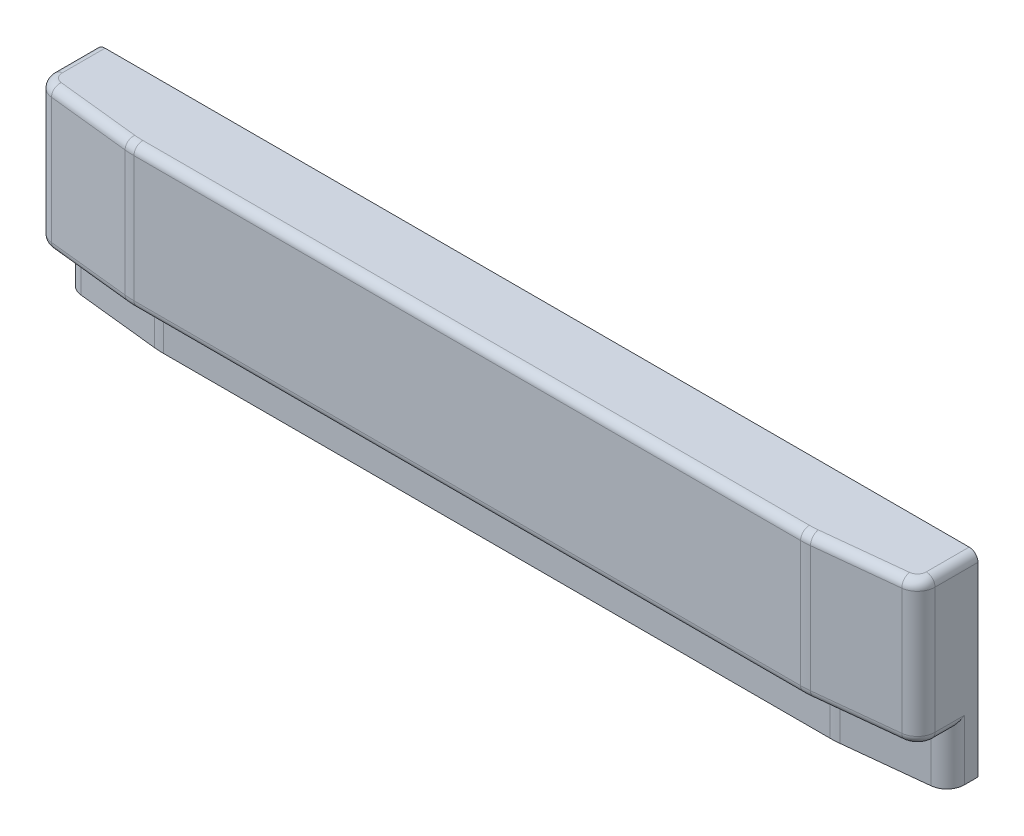
SolidWorks part; units mm, degrees
ref_plane "Front Plane" through (0, 0, 0) normal (0, 0, 1) x (1, 0, 0)
ref_plane "Top Plane" through (0, 0, 0) normal (0, 1, 0) x (1, 0, 0)
ref_plane "Right Plane" through (0, 0, 0) normal (1, 0, 0) x (0, 0, -1)
sketch "Sketch7" plane through (0, 0, 0) normal (0, 1, 0) x (1, 0, 0)
  line L0 (0, 0) -> (762, 0)
  line L1 (762, 0) -> (762, -50.8)
  line L2 (762, -50.8) -> (673.1, -60.325)
  line L3 (673.1, -60.325) -> (88.9, -60.325)
  line L4 (88.9, -60.325) -> (0, -50.8)
  line L5 (0, -50.8) -> (0, 0)
  dimension "D1" = 762
  dimension "D2" = 50.8
  dimension "D3" = 88.9
  dimension "D4" = 88.9
  dimension "D5" = 60.325
extrude "Boss-Extrude1" add sketch "Sketch7" along normal blind 168.275
ref_plane "Wall Plane" through (0, 0, 0) normal (0, 0, 1) x (1, 0, 0)
ref_plane "Floor Plane" through (0, 0, 0) normal (0, 1, 0) x (1, 0, 0)
sketch "Sketch10" plane through (0, 0, 0) normal (0, -1, 0) x (1, 0, 0)
  line L0 (0, 50.8) -> (0, 25.4)
  line L1 (0, 0) -> (0, 50.8) construction
  line L2 (0, 25.4) -> (88.9, 34.925)
  line L3 (88.9, 34.925) -> (673.1, 34.925)
  line L4 (673.1, 34.925) -> (762, 25.4)
  line L5 (762, 50.8) -> (762, 0) construction
  line L6 (762, 25.4) -> (762, 50.8)
  line L7 (762, 50.8) -> (673.1, 60.325)
  line L8 (673.1, 60.325) -> (88.9, 60.325)
  line L9 (88.9, 60.325) -> (0, 50.8)
  dimension "D1" = 25.4
extrude "Cut-Extrude1" cut sketch "Sketch10" against normal blind 44.45
fillet "Fillet1" radius 15.24 4 edges at (762, 22.225, 25.4) (762, 106.3625, 50.8) (0, 22.225, 25.4) (0, 106.3625, 50.8)
fillet "Fillet2" radius 76.2 4 edges at (673.1, 22.225, 34.925) (673.1, 106.3625, 60.325) (88.9, 22.225, 34.925) (88.9, 106.3625, 60.325)
fillet "Fillet3" radius 7.62 9 edges at (0, 168.275, 18.5528) (3.9042, 168.275, 47.2918) (49.2346, 168.275, 56.0751) (88.9058, 168.275, 60.2165) (762, 168.275, 18.5528) (758.0958, 168.275, 47.2918) (712.7654, 168.275, 56.0751) (673.0942, 168.275, 60.2165) (381, 168.275, 60.325)
fillet "Fillet4" radius 7.62 9 edges at (762, 44.45, 24.4056) (758.0958, 44.45, 47.2918) (712.7654, 44.45, 56.0751) (673.0942, 44.45, 60.2165) (0, 44.45, 24.4056) (3.9042, 44.45, 47.2918) (49.2346, 44.45, 56.0751) (88.9058, 44.45, 60.2165) (381, 44.45, 60.325)
